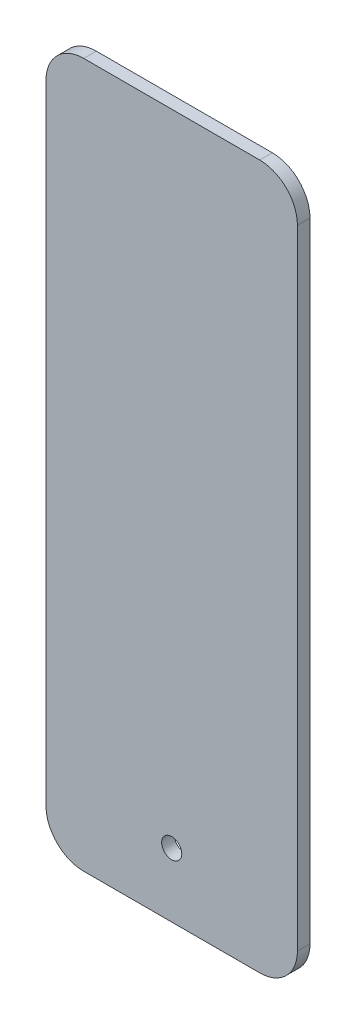
SolidWorks part; units mm, degrees
material "Oak"
ref_plane "Front Plane" through (0, 0, 0) normal (0, 0, 1) x (1, 0, 0)
ref_plane "Top Plane" through (0, 0, 0) normal (0, 1, 0) x (1, 0, 0)
ref_plane "Right Plane" through (0, 0, 0) normal (1, 0, 0) x (0, 0, -1)
sketch "Sketch1" plane through (0, 0, 0) normal (0, 0, 1) x (1, 0, 0)
  line L1 (-35, 140) -> (35, 140)
  line L2 (-50, 125) -> (-50, -125)
  line L3 (-35, -140) -> (35, -140)
  line L4 (50, 125) -> (50, -125)
  line L5 (-50, 140) -> (50, -140) construction
  line L6 (-50, -140) -> (50, 140) construction
  arc A0 (35, 140) -> (50, 125) centre (35, 125) cw
  arc A1 (-35, 140) -> (-50, 125) centre (-35, 125) ccw
  arc A2 (-50, -125) -> (-35, -140) centre (-35, -125) ccw
  arc A3 (35, -140) -> (50, -125) centre (35, -125) ccw
  circle A4 centre (0, -114.5376) radius 4
  point P0 (0, 0)
  dimension "D3" = 15
  dimension "D4" = 8
  dimension "D1" = 280
  dimension "D2" = 100
base flange "Base-Flange1" sketch "Sketch1" thickness 5 reverse thickness direction no parameters "D1"=0.7366
sketch "Bend-Lines1" [suppressed] plane through (0, 0, 0) normal (0, 1, 0) x (1, 0, 0)
sketch "Bounding-Box1" [suppressed] plane through (0, 0, 0) normal (0, 1, 0) x (1, 0, 0)
sheet metal parameters "Sheet-Metal1" thickness 5 parameters "D1"=0.7366
flat pattern "Flat-Pattern1" [suppressed]
sketch "Bend-Lines2" plane through (0, 0, 0) normal (0, 1, 0) x (1, 0, 0)
sketch3d "Bounding-Box2" [suppressed]
  line L0 (15, -265, 0) -> (15, 15, 0) construction
  line L1 (-85, -265, 0) -> (-85, 15, 0) construction
  line L2 (15, -265, 0) -> (-85, -265, 0) construction
  line L3 (15, 15, 0) -> (-85, 15, 0) construction
